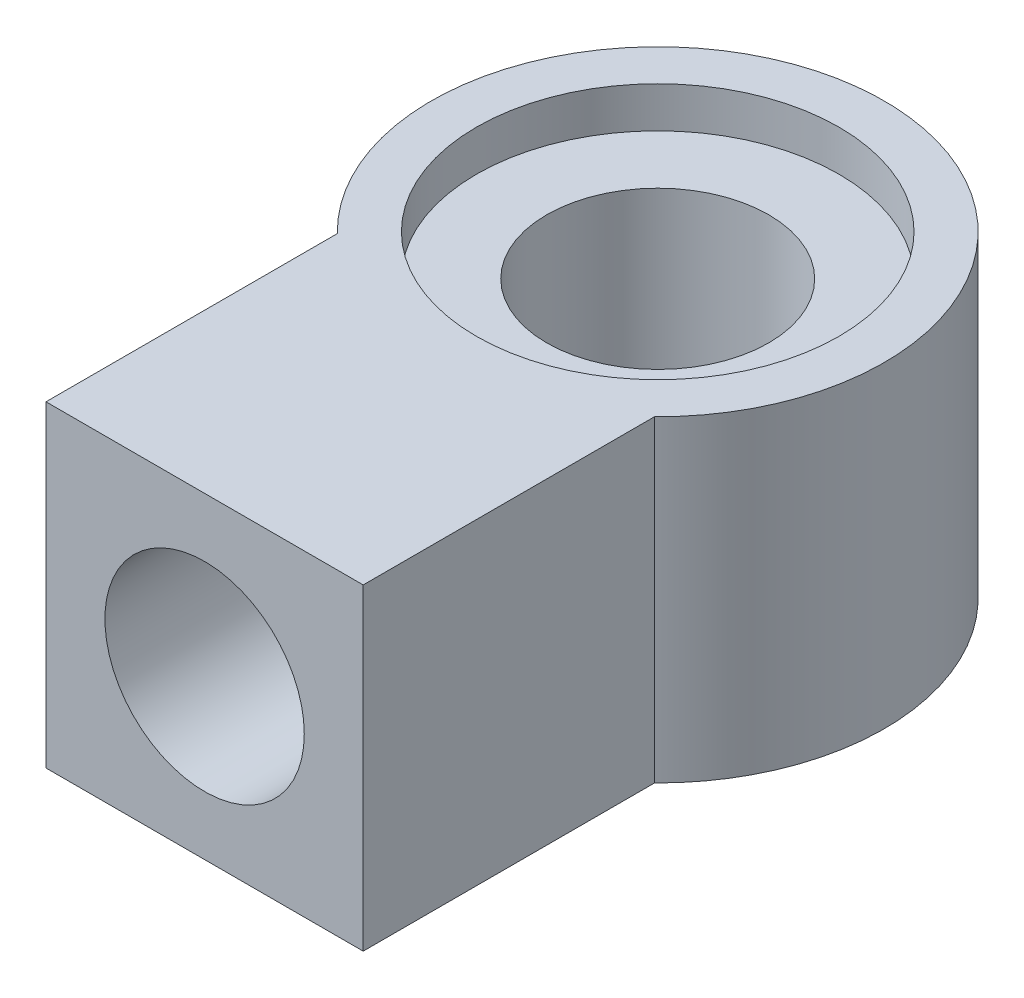
SolidWorks part; units mm, degrees
ref_plane "Front Plane" through (0, 0, 0) normal (0, 0, 1) x (1, 0, 0)
ref_plane "Top Plane" through (0, 0, 0) normal (0, 1, 0) x (1, 0, 0)
ref_plane "Right Plane" through (0, 0, 0) normal (1, 0, 0) x (0, 0, -1)
sketch "Sketch1" plane through (0, 0, 0) normal (0, 1, 0) x (1, 0, 0)
  circle A0 centre (0, 0) radius 5
  circle A1 centre (0, 0) radius 2.45
  dimension "D1" = 10
  dimension "D2" = 4.9
extrude "Boss-Extrude1" add sketch "Sketch1" along normal blind 7
ref_plane "Plane1" through (0, 0, 5) normal (0, 0, 1) x (1, 0, 0)
sketch "Sketch2" plane through (0, 0, 5) normal (0, 0, 1) x (1, 0, 0)
  line L0 (5, 7) -> (-5, 7) construction
  line L1 (3.5, 7) -> (-3.5, 7)
  line L2 (0, 7) -> (0, 0)
  line L3 (3.5, 0) -> (-3.5, 0)
  line L4 (-3.5, 7) -> (-3.5, 0)
  line L5 (-5, 0) -> (5, 0) construction
  line L6 (3.5, 7) -> (3.5, 0)
  dimension "D1" = 3.5
extrude "Boss-Extrude3" add sketch "Sketch2" against normal blind 1.5 contours L1 L4 L3 L2 | L6 L1 L2 L3 region at (1.75, 3.5, 5) region at (-1.75, 3.5, 5)
sketch "Sketch4" plane through (0, 0, 5) normal (0, 0, 1) x (1, 0, 0)
  line L1 (-3.5, 7) -> (3.5, 7)
  line L2 (-3.5, 7) -> (-3.5, 0)
  line L3 (-3.5, 0) -> (3.5, 0)
  line L4 (3.5, 7) -> (3.5, 0)
  circle A0 centre (0, 3.5) radius 2.2
  dimension "D1" = 4.4
extrude "Boss-Extrude4" add sketch "Sketch4" along normal blind 5
sketch "Sketch5" plane through (0, 7, 0) normal (0, 1, 0) x (1, 0, 0)
  circle A0 centre (0, 0) radius 4
  dimension "D1" = 8
extrude "Cut-Extrude1" cut sketch "Sketch5" against normal blind 0.9
